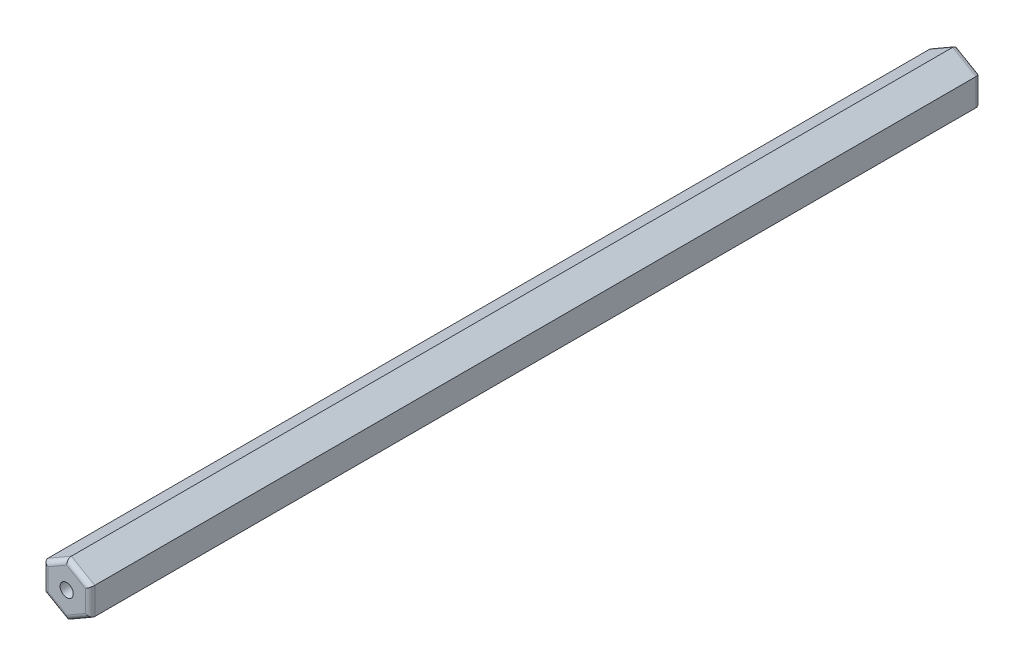
SolidWorks part; units mm, degrees
ref_plane "Plano frontal" through (0, 0, 0) normal (0, 0, 1) x (1, 0, 0)
ref_plane "Plano superior" through (0, 0, 0) normal (0, 1, 0) x (1, 0, 0)
ref_plane "Plano direito" through (0, 0, 0) normal (1, 0, 0) x (0, 0, -1)
ref_plane "Plano1" through (0, 0, 135) normal (0, 0, 1) x (1, 0, 0)
sketch "Esboço1" plane through (0, 0, 135) normal (0, 0, 1) x (1, 0, 0)
  line L0 (-55.0021, 2.8868) -> (-57.5021, 1.4434)
  line L1 (-57.5021, 1.4434) -> (-57.5021, -1.4434)
  line L2 (-57.5021, -1.4434) -> (-55.0021, -2.8868)
  line L3 (-55.0021, -2.8868) -> (-52.5021, -1.4434)
  line L4 (-52.5021, -1.4434) -> (-52.5021, 1.4434)
  line L5 (-52.5021, 1.4434) -> (-55.0021, 2.8868)
  line L6 (-55.0021, 2.8868) -> (-55.0021, -2.8868) construction
  circle A0 centre (-55.0021, 0) radius 2.8868 construction
  dimension "D1" = 5
extrude "Ressalto-extrusão1" add sketch "Esboço1" against normal blind 95
fillet "Filete1" radius 0.5 12 edges at (-53.7521, -2.1651, 135) (-56.2521, -2.1651, 135) (-52.5021, 0, 135) (-57.5021, 0, 135) (-53.7521, 2.1651, 135) (-56.2521, 2.1651, 135) (-53.7521, -2.1651, 40) (-56.2521, -2.1651, 40) (-52.5021, 0, 40) (-57.5021, 0, 40) (-53.7521, 2.1651, 40) (-56.2521, 2.1651, 40)
sketch "Esboço2" plane through (0, 0, 135) normal (0, 0, 1) x (1, 0, 0)
  line L0 (-53.0021, -1.1547) -> (-53.0021, 1.1547) construction
  circle A0 centre (-55.0021, 0) radius 0.7015
  point P2 (-53.0021, 0)
  point P3 (0, 0)
extrude "Corte-extrusão1" cut sketch "Esboço2" against normal through all
